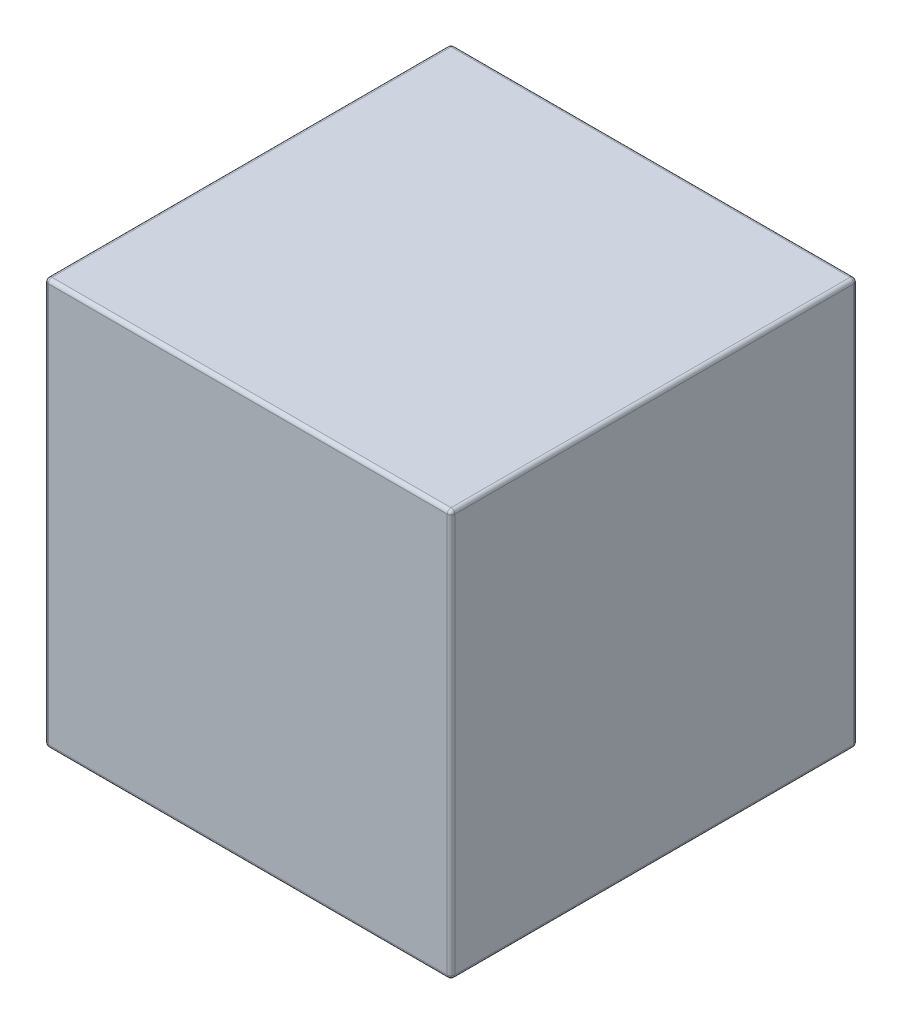
SolidWorks part; units mm, degrees
ref_plane "Plan de face" through (0, 0, 0) normal (0, 0, 1) x (1, 0, 0)
ref_plane "Plan de dessus" through (0, 0, 0) normal (0, 1, 0) x (1, 0, 0)
ref_plane "Plan de droite" through (0, 0, 0) normal (1, 0, 0) x (0, 0, -1)
sketch "Esquisse1" plane through (0, 0, 0) normal (0, 0, 1) x (1, 0, 0)
  line L1 (0, 0) -> (54, 0)
  line L2 (0, 0) -> (0, -54)
  line L3 (0, -54) -> (54, -54)
  line L4 (54, 0) -> (54, -54)
  dimension "D1" = 54
  dimension "D2" = 54
extrude "Boss.-Extru.1" add sketch "Esquisse1" along normal blind 54
sketch "Esquisse2" plane through (0, -54, 0) normal (0, -1, 0) x (1, 0, 0)
  line L0 (54, 54) -> (54, 0) construction
  line L1 (21.75, 51) -> (32.25, 51)
  line L2 (21.75, 51) -> (21.75, 40.5)
  line L3 (21.75, 40.5) -> (32.25, 40.5)
  line L4 (32.25, 51) -> (32.25, 40.5)
  line L5 (0, 54) -> (54, 54) construction
  line L13 (37.5, 32.25) -> (48, 32.25)
  line L14 (37.5, 32.25) -> (37.5, 21.75)
  line L15 (37.5, 21.75) -> (48, 21.75)
  line L16 (48, 32.25) -> (48, 21.75)
  point P4 (48, 27)
  point P7 (54, 27)
  point P8 (27, 51)
  point P11 (27, 54)
  dimension "D1" = 10.5
  dimension "D2" = 10.5
  dimension "D3" = 10.5
  dimension "D4" = 10.5
  dimension "D5" = 0
  dimension "D6" = 0
  dimension "D7" = 13.5
  dimension "D8" = 10.5
extrude "Enlèv. mat.-Extru.1" cut sketch "Esquisse2" against normal blind 4.5
ref_plane "Plan1" through (0, 0, 27) normal (0, 0, 1) x (1, 0, 0)
ref_plane "Plan2" through (27, 0, 0) normal (1, 0, 0) x (0, 0, -1)
ref_plane "Plan3" through (27, 0, 27) normal (0.7071, 0, 0.7071) x (0.7071, 0, -0.7071)
fillet "Congé1" radius 0.5 12 edges at (0, -54, 27) (27, -54, 54) (0, -27, 54) (54, -54, 27) (54, -27, 54) (27, -54, 0) (54, -27, 0) (0, -27, 0) (54, 0, 27) (27, 0, 54) (0, 0, 27) (27, 0, 0)
mirror "Symétrie1" about plane through (0, 0, 27) normal (0, 0, 1) of "Enlèv. mat.-Extru.1"
mirror "Symétrie2" about plane through (27, 0, 0) normal (1, 0, 0) of "Symétrie1"
